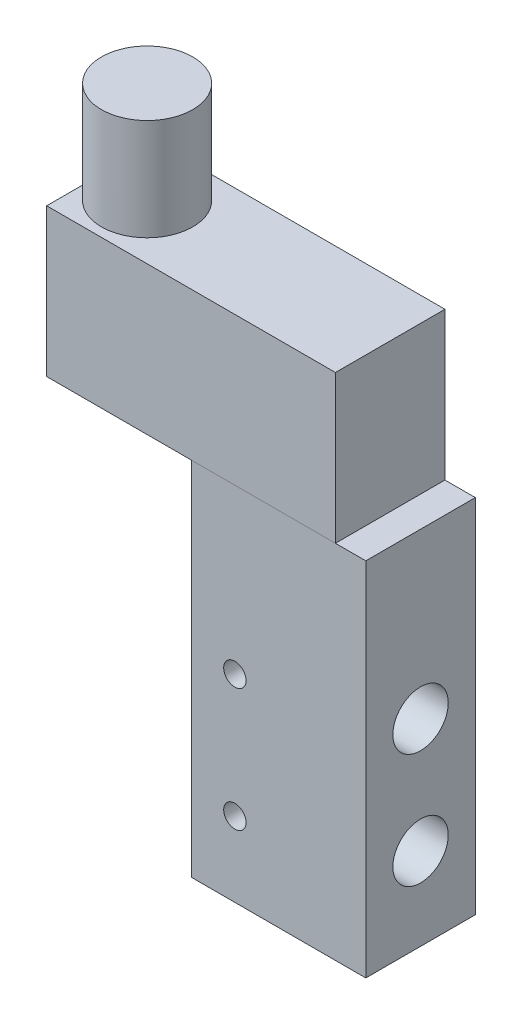
SolidWorks part; units mm, degrees
material "5454-O"
ref_plane "Front" through (0, 0, 0) normal (0, 0, 1) x (1, 0, 0)
ref_plane "Top" through (0, 0, 0) normal (0, 1, 0) x (1, 0, 0)
ref_plane "Right" through (0, 0, 0) normal (1, 0, 0) x (0, 0, -1)
ref_axis "Axis1" through (0, 0, 55) along (0, 0, -1)
sketch "Sketch1" plane through (0, 0, 0) normal (0, 0, 1) x (1, 0, 0)
  line L1 (-17.5, 36.285) -> (17.5, 36.285)
  line L2 (-17.5, 36.285) -> (-17.5, -36.285)
  line L3 (-17.5, -36.285) -> (17.5, -36.285)
  line L4 (17.5, 36.285) -> (17.5, -36.285)
  line L5 (-17.5, 36.285) -> (17.5, -36.285) construction
  line L6 (-17.5, -36.285) -> (17.5, 36.285) construction
  point P0 (0, 0)
  dimension "D1" = 72.57
  dimension "D2" = 35
extrude "Boss-Extrude1" add sketch "Sketch1" along normal blind 22
sketch "Sketch2" plane through (0, 36.285, 0) normal (0, 1, 0) x (1, 0, 0)
  line L0 (17.5, 0) -> (-17.5, 0) construction
  line L1 (11.4, 0) -> (-46.6, 0)
  line L2 (11.4, 0) -> (11.4, -22)
  line L3 (11.4, -22) -> (-46.6, -22)
  line L4 (-46.6, 0) -> (-46.6, -22)
  line L5 (17.5, -22) -> (-17.5, -22) construction
  line L6 (17.5, -22) -> (17.5, 0) construction
  dimension "D1" = 6.1
  dimension "D2" = 58
extrude "Boss-Extrude2" add sketch "Sketch2" along normal blind 29.71
sketch "Sketch3" plane through (0, 36.285, 0) normal (0, -1, 0) x (1, 0, 0)
  line L0 (-46.6, 11) -> (-17.5, 11) construction
  line L1 (-46.6, 0) -> (-46.6, 22) construction
  line L2 (-17.5, 22) -> (-17.5, 0) construction
  circle A0 centre (-37.425, 11) radius 9.175
  dimension "D1" = 18.35
extrude "Boss-Extrude3" add sketch "Sketch3" against normal blind 50.11
hole_wizard "M4 Clearance Hole1" positions "Sketch5" profile "Sketch6" hole size "M4" standard "ANSI Metric" end condition through all
sketch "Sketch5" plane through (0, 0, 22) normal (0, 0, 1) x (1, 0, 0)
  line L0 (-8.8, 3.415) -> (-8.8, -21.285) construction
  line L2 (-17.5, 36.285) -> (-17.5, -36.285) construction
  line L3 (-17.5, -36.285) -> (17.5, -36.285) construction
  point P0 (-8.8, 3.415)
  point P2 (-8.8, -21.285)
  dimension "D1" = 24.7
  dimension "D2" = 8.7
  dimension "D3" = 15
sketch "Sketch6" plane through (-8.8, 3.415, 22) normal (1, 0, 0) x (0, -1, 0)
  line L0 (0, 0) -> (0, 22)
  line L1 (0, 22) -> (2.25, 22)
  line L2 (2.25, 22) -> (2.25, 0)
  line L5 (2.25, 0) -> (0, 0)
  line L11 (0, -6.35) -> (0, 107.95) construction
  dimension "Thru Hole Dia." = 4.5
  dimension "Thru Hole Depth" = 22
hole_wizard "Pipe Tap Drill for 1/4 Tap1" positions "Sketch7" profile "Sketch8" hole size "1/4" standard "ANSI Inch"
sketch "Sketch7" plane through (-17.5, 0, 0) normal (-1, 0, 0) x (0, 0, 1)
  line L0 (11, -36.285) -> (11, 36.285) construction
  line L1 (22, -36.285) -> (0, -36.285) construction
  line L2 (22, 36.285) -> (0, 36.285) construction
  point P0 (11, -7.985)
  dimension "D1" = 28.3
sketch "Sketch8" plane through (-17.5, -7.985, 11) normal (0, 1, 0) x (0, 0, 1)
  line L0 (0, 0) -> (0, 18.3423)
  line L1 (0, 18.3423) -> (5.5626, 15)
  line L2 (5.5626, 15) -> (5.5626, 0)
  line L5 (5.5626, 0) -> (0, 0)
  line L10 (0, 18.3423) -> (-5.5626, 15) construction
  line L11 (0, -6.35) -> (0, 107.95) construction
  dimension "Hole Dia." = 11.1252
  dimension "Hole Depth" = 15
  dimension "Drill Angle" = 118
hole_wizard "Pipe Tap Drill for 1/4 Tap2" positions "Sketch9" profile "Sketch10" hole size "1/4" standard "ANSI Inch"
sketch "Sketch9" plane through (17.5, 0, 0) normal (1, 0, 0) x (0, 0, -1)
  line L0 (-11, -36.285) -> (-11, 36.285) construction
  line L1 (-22, -36.285) -> (0, -36.285) construction
  line L2 (-22, 36.285) -> (0, 36.285) construction
  point P0 (-11, 3.315)
  point P2 (-11, -19.685)
  dimension "D1" = 16.6
  dimension "D2" = 23
sketch "Sketch10" plane through (17.5, 3.315, 11) normal (0, 1, 0) x (0, 0, -1)
  line L0 (0, 0) -> (0, 18.3423)
  line L1 (0, 18.3423) -> (5.5626, 15)
  line L2 (5.5626, 15) -> (5.5626, 0)
  line L5 (5.5626, 0) -> (0, 0)
  line L10 (0, 18.3423) -> (-5.5626, 15) construction
  line L11 (0, -6.35) -> (0, 107.95) construction
  dimension "Hole Dia." = 11.1252
  dimension "Hole Depth" = 15
  dimension "Drill Angle" = 118
sketch "Sketch11" plane through (0, 0, 22) normal (0, 0, 1) x (1, 0, 0)
  line L0 (-17.5, 36.285) -> (11.8936, 36.285)
  line L1 (17.5, 36.285) -> (11.4, 36.285) construction
sketch "Sketch12" plane through (0, 0, 0) normal (0, 0, -1) x (-1, 0, 0)
  line L0 (-11.4, 36.285) -> (17.5, 36.285)
split line "Split Line1"
split line "Split Line2"
sketch "Sketch13" plane through (0, -36.285, 0) normal (0, -1, 0) x (1, 0, 0)
  line L4 (-17.5, 0) -> (17.5, 0)
  line L5 (17.5, 0) -> (17.5, 22)
  line L6 (17.5, 22) -> (-17.5, 22)
  line L7 (-17.5, 22) -> (-17.5, 0)
  line L8 (-17.5, 0) -> (17.5, 0)
  line L9 (17.5, 0) -> (17.5, 22)
  line L10 (17.5, 22) -> (-17.5, 22)
  line L11 (-17.5, 22) -> (-17.5, 0)
  dimension "D1" = 0
